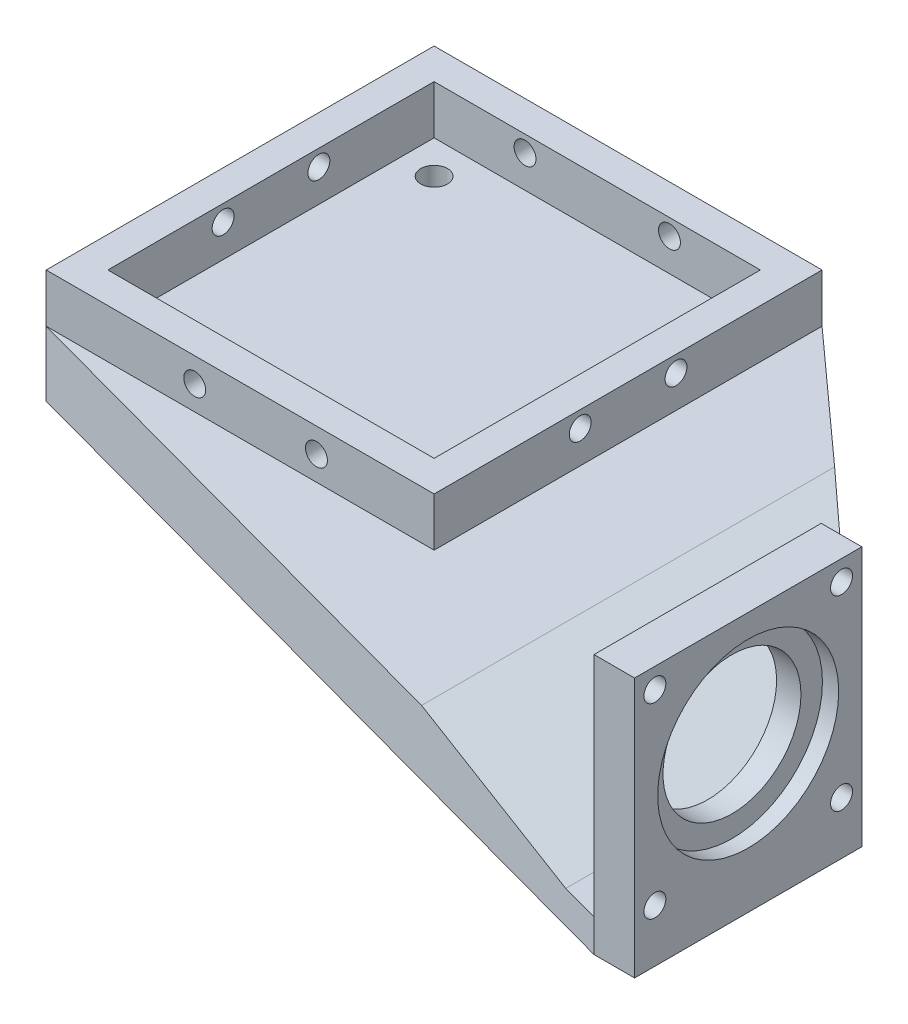
SolidWorks part; units mm, degrees
ref_plane "Front Plane" through (0, 0, 0) normal (0, 0, 1) x (1, 0, 0)
ref_plane "Top Plane" through (0, 0, 0) normal (0, 1, 0) x (1, 0, 0)
ref_plane "Right Plane" through (0, 0, 0) normal (1, 0, 0) x (0, 0, -1)
sketch "Sketch1" plane through (0, 0, 0) normal (0, 1, 0) x (1, 0, 0)
  line L0 (-20.1, 20.1) -> (20.1, -20.1) construction
  line L1 (-20.1, 20.1) -> (20.1, 20.1)
  line L2 (-20.1, 20.1) -> (-20.1, -20.1)
  line L3 (-20.1, -20.1) -> (20.1, -20.1)
  line L4 (20.1, 20.1) -> (20.1, -20.1)
  line L5 (-20.1, -20.1) -> (20.1, 20.1) construction
  line L6 (-23.9, 23.9) -> (-23.9, -23.9)
  line L7 (-23.9, -23.9) -> (23.9, -23.9)
  line L8 (23.9, 23.9) -> (23.9, -23.9)
  line L9 (-23.9, 23.9) -> (23.9, 23.9)
  point P4 (0, 0)
  dimension "D1" = 40.2
  dimension "D2" = 40.2
  dimension "D3" = 3.8
extrude "Boss-Extrude1" add sketch "Sketch1" along normal blind 6
sketch "Sketch6" plane through (0, 0, -23.9) normal (0, 0, -1) x (-1, 0, 0)
  line L0 (-8.9, 4) -> (8.9, 4) construction
  line L1 (23.9, 6) -> (23.9, 0) construction
  line L2 (-23.9, 6) -> (23.9, 6) construction
  circle A0 centre (-8.9, 4) radius 1.35
  circle A1 centre (8.9, 4) radius 1.35
  point P4 (0, 4)
  dimension "D3" = 2.7
  dimension "D4" = 2.7
  dimension "D1" = 15
  dimension "D2" = 2
extrude "Cut-Extrude4" cut sketch "Sketch6" against normal up to next
sketch "Sketch7" plane through (0, 0, 23.9) normal (0, 0, 1) x (1, 0, 0)
  line L0 (23.9, 6) -> (23.9, 0) construction
  line L1 (-23.9, 6) -> (-23.9, 0) construction
  line L2 (-23.9, 6) -> (-23.9, 0) construction
  circle A0 centre (9.4, 3) radius 1.35
  circle A1 centre (-5.6, 3) radius 1.35
  point P9 (-23.9, 3)
  dimension "D1" = 2.7
  dimension "D2" = 2.7
  dimension "D3" = 14.5
  dimension "D4" = 15
extrude "Cut-Extrude5" cut sketch "Sketch7" against normal up to next
sketch "Sketch8" plane through (23.9, 0, 0) normal (1, 0, 0) x (0, 0, -1)
  line L0 (-23.9, 6) -> (-23.9, 0) construction
  line L2 (0, 0) -> (0, 6) construction
  line L3 (-23.9, 6) -> (23.9, 6) construction
  circle A0 centre (-5.9, 4) radius 1.35
  circle A3 centre (5.9, 4) radius 1.35
  dimension "D3" = 2.7
  dimension "D1" = 18
  dimension "D2" = 2
extrude "Cut-Extrude6" cut sketch "Sketch8" against normal through all
sketch "Sketch10" plane through (23.9, 0, 0) normal (1, 0, 0) x (0, 0, -1)
  line L3 (-20.1, 0) -> (-49.9314, 0)
  line L6 (-23.9, 0) -> (23.9, 0) construction
  line L7 (-20.1, 0) -> (-20.1, 6)
  line L8 (-20.1, 6) -> (20.1, 6) construction
  line L9 (-20.1, 6) -> (20.1, 6) construction
  line L10 (-49.9314, 7.235) -> (-49.9314, 0)
  line L13 (-49.9314, 7.235) -> (-45.1764, 16.4549)
  line L14 (-45.1764, 16.4549) -> (-44.2876, 15.9965)
  line L15 (-25.4, 11.4128) -> (-24.4, 11.4128)
  line L16 (-20.1, 6) -> (-24.4, 6)
  line L17 (-24.4, 6) -> (-24.4, 11.4128)
  circle A0 centre (-35.4, 11.4128) radius 8.5 construction
  arc A2 (-44.2876, 15.9965) -> (-25.4, 11.4128) centre (-35.4, 11.4128) ccw
  arc A3 (-45.1764, 16.4549) -> (-24.4, 11.4128) centre (-35.4, 11.4128) ccw construction
  point P1 (0, 0)
  dimension "D2" = 17
  dimension "D1" = 20
  dimension "D3" = 22
  dimension "D5" = 5.4128
  dimension "D6" = 15.3
  dimension "D7" = 0.5
sketch "Sketch11" plane through (0, 0, 0) normal (0, 1, 0) x (1, 0, 0)
  line L0 (20.1, 20.1) -> (-20.1, 20.1) construction
  line L1 (-20.1, 20.1) -> (-20.1, -20.1) construction
  line L3 (23.9, -23.9) -> (23.9, 23.9) construction
  line L4 (73.9, -21.2) -> (68.9, -21.2)
  line L5 (73.9, -21.2) -> (73.9, -49.2)
  line L6 (73.9, -49.2) -> (68.9, -49.2)
  line L7 (68.9, -21.2) -> (68.9, -49.2)
  line L8 (68.9, -49.2) -> (-23.9, -23.9)
  line L9 (23.9, 23.9) -> (-23.9, 23.9)
  line L10 (23.9, 23.9) -> (23.9, -23.9)
  line L11 (23.9, -23.9) -> (-23.9, -23.9)
  line L12 (-23.9, 23.9) -> (-23.9, -23.9)
  line L13 (73.9, -21.2) -> (23.9, 23.9)
  circle A0 centre (-16, 16) radius 1.65
  circle A1 centre (16, 16) radius 1.65
  circle A2 centre (16, -16) radius 1.65
  circle A3 centre (-16, -16) radius 1.65
  point P24 (23.9, -35.4)
  point P26 (68.9, -33.8538)
  point P27 (68.9, -35.2)
  dimension "D3" = 3.3
  dimension "D1" = 4.1
  dimension "D2" = 4.1
  dimension "D6" = 32
  dimension "D7" = 32
  dimension "D8" = 50
  dimension "D9" = 5
  dimension "D10" = 28
  dimension "D11" = 0.2
  dimension "D4" = 2
  dimension "D5" = 2
extrude "Boss-Extrude8" add sketch "Sketch11" against normal blind 8 contours L4 L13 L10 L11 L8 L7 | L4 L7 L6 L5 | L9 L12 L11 L10 A3 A2 A1 A0 region at (71.4, 0, 35.2) region at (39.5995, 0, 19.6661) region at (0, 0, 0)
sketch "Sketch12" plane through (73.9, 0, 0) normal (1, 0, 0) x (0, 0, -1)
  line L0 (-46.7, 21.5128) -> (-23.7, 21.5128) construction
  line L1 (-21.2, -3.9872) -> (-49.2, -3.9872)
  line L2 (-21.2, -3.9872) -> (-21.2, 24.0128)
  line L3 (-21.2, 24.0128) -> (-49.2, 24.0128)
  line L4 (-49.2, -3.9872) -> (-49.2, 24.0128)
  line L5 (-21.2, -3.9872) -> (-49.2, 24.0128) construction
  line L6 (-21.2, 24.0128) -> (-49.2, -3.9872) construction
  line L7 (-46.7, 21.5128) -> (-46.7, -1.4872) construction
  circle A0 centre (-35.2, 10.0128) radius 8.5
  circle A2 centre (-35.2, 10.0128) radius 11.15
  circle A3 centre (-46.7, 21.5128) radius 1.35
  circle A4 centre (-23.7, 21.5128) radius 1.35
  circle A5 centre (-23.7, -1.4872) radius 1.35
  circle A6 centre (-46.7, -1.4872) radius 1.35
  point P0 (-35.2, 10.0128)
  point P10 (0, 0)
  point P11 (0, 0)
  point P21 (0, 0)
  point P22 (-34.6893, 13.3027)
  point P24 (-35.4, 11.4128)
  point P26 (-35.2, 13.3027)
  point P27 (-35.2, 10.0679)
  line M2 (-21.2, 0) -> (-49.2, 0)
  line M3 (-49.2, 0) -> (-49.2, -8)
  line M5 (-21.2, -8) -> (-21.2, 0)
  dimension "D1" = 22.3
  dimension "D4" = 2.7
  dimension "D10" = 17
  dimension "D2" = 28
  dimension "D3" = 28
  dimension "D7" = 23
  dimension "D8" = 23
  dimension "D9" = 11.5
  dimension "D11" = 0.2
  dimension "D12" = 1.4
  dimension "D5" = 2
  dimension "D6" = 2
sketch "Sketch13" plane through (0, 0, 49.2) normal (0, 0, 1) x (1, 0, 0)
  line L1 (73.9, -3.9872) -> (64.1144, -3.9872)
  line L2 (73.9, -3.9872) -> (73.9, 1.7874)
  line L3 (73.9, 1.7874) -> (28.7381, 1.7874)
  line L4 (64.1144, -3.9872) -> (28.7381, 1.7874)
  line L5 (73.9, -8) -> (73.9, 0) construction
extrude "Cut-Extrude7" cut sketch "Sketch13" against normal through all
extrude "Boss-Extrude9" add sketch "Sketch12" against normal blind 5 contours A6 A2 A5 L2 L3 L4 A4 A3 M2 | A6 L1 A5 A2 M2 M3 M5 region at (73.9, -2.1808, 35.2) region at (73.9, 0.3689, 25.7471)
extrude "Boss-Extrude10" add sketch "Sketch12<3>" against normal blind 3 from offset 2 contours A2 A0 M2 | A2 M2 region at (73.9, 0.3074, 35.2) region at (73.9, -0.4569, 35.2) offset against normal yes
sketch "Sketch12<3>" plane through (73.9, 0, 0) normal (1, 0, 0) x (0, 0, -1) same geometry as "Sketch12"
